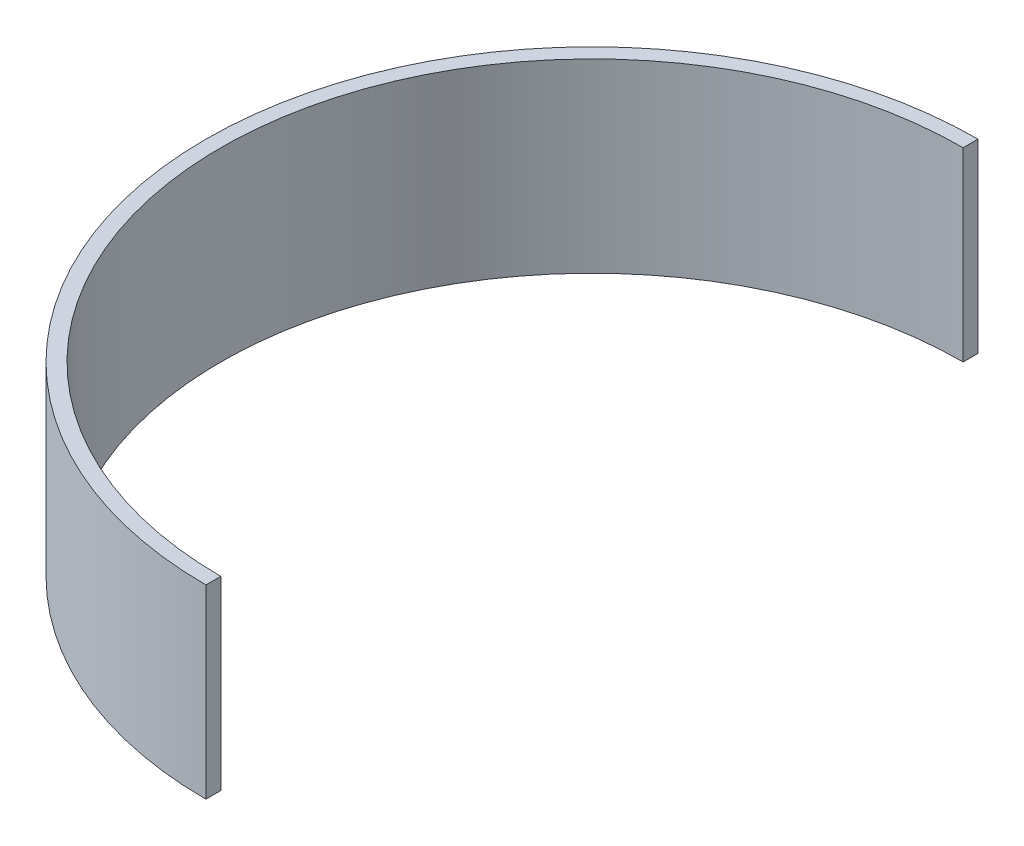
SolidWorks part; units mm, degrees
other "标注1"
sketch "草图15" plane through (-5.2, 2.5, -5.2) normal (0, 1, 0) x (1, 0, 0)
ref_plane "前视基准面" through (0, 0, 0) normal (0, 0, 1) x (1, 0, 0)
ref_plane "上视基准面" through (0, 0, 0) normal (0, 1, 0) x (1, 0, 0)
ref_plane "右视基准面" through (0, 0, 0) normal (1, 0, 0) x (0, 0, -1)
other "Configuration Table"
sketch "草图8" plane through (0, 0, 0) normal (0, 1, 0) x (1, 0, 0)
  line L1 (0, -8.527) -> (13.1111, -8.527)
  line L2 (0, -8.527) -> (0, 8.3123)
  line L3 (0, 8.3123) -> (13.1111, 8.3123)
  line L4 (13.1111, -8.527) -> (13.1111, 8.3123)
  circle A0 centre (0, 0) radius 5
  circle A1 centre (0, 0) radius 5.2
  point P8 (0, 0)
extrude "凸台-拉伸4" add sketch "草图8" along normal blind 2.5 contours A1
sketch "草图11" plane through (0, 0, 0) normal (0, 1, 0) x (1, 0, 0)
  circle A0 centre (0, 0) radius 5
extrude "切除-拉伸8" cut sketch "草图11" against normal blind 2.5 and the other way blind 2.5
sketch "草图12" plane through (0, 0, 0) normal (0, 1, 0) x (1, 0, 0)
  line L1 (0, 6.9707) -> (11.1015, 6.9707)
  line L2 (0, 6.9707) -> (0, -10.4561)
  line L3 (0, -10.4561) -> (11.1015, -10.4561)
  line L4 (11.1015, 6.9707) -> (11.1015, -10.4561)
extrude "切除-拉伸9" cut sketch "草图12" against normal blind 2.5 and the other way blind 2.5
sketch "草图14" plane through (0, 0, 0) normal (0, 1, 0) x (1, 0, 0)
  line L1 (0, 5.2) -> (10.0111, 5.2)
  line L2 (0, 5.2) -> (0, -5.2)
  line L3 (0, -5.2) -> (10.0111, -5.2)
  line L4 (10.0111, 5.2) -> (10.0111, -5.2)
  circle A0 centre (0, 0) radius 5
  circle A1 centre (0, 0) radius 5.2
